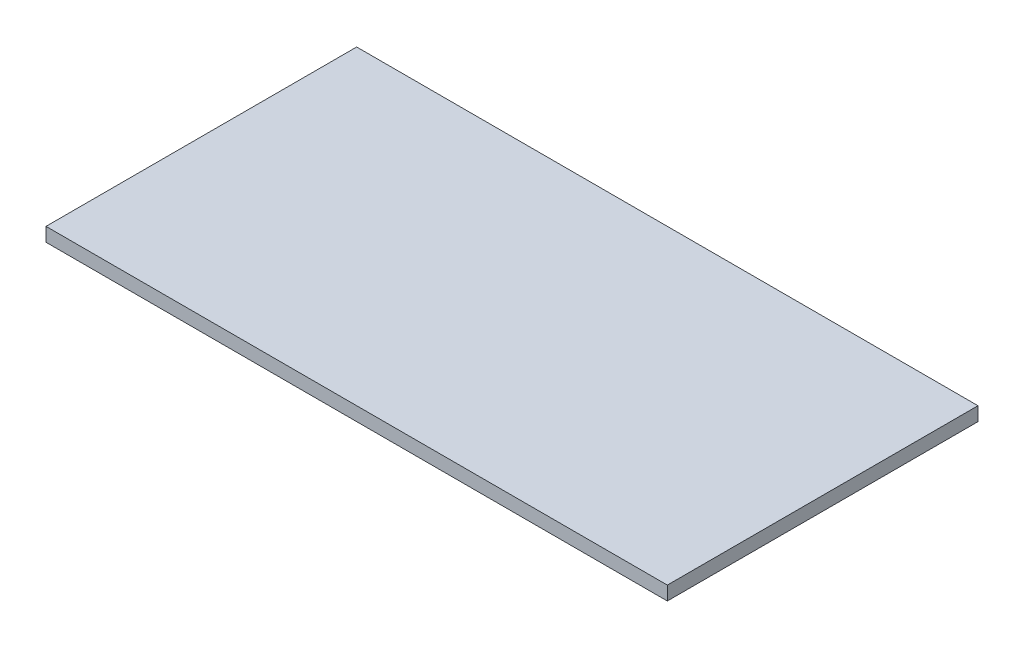
SolidWorks part; units mm, degrees
material "Cedar"
ref_plane "Front Plane" through (0, 0, 0) normal (0, 0, 1) x (1, 0, 0)
ref_plane "Top Plane" through (0, 0, 0) normal (0, 1, 0) x (1, 0, 0)
ref_plane "Right Plane" through (0, 0, 0) normal (1, 0, 0) x (0, 0, -1)
sketch "Sketch1" plane through (0, 0, 0) normal (0, 0, 1) x (1, 0, 0)
  line L1 (-285.75, -6.35) -> (285.75, -6.35)
  line L2 (-285.75, -6.35) -> (-285.75, 6.35)
  line L3 (-285.75, 6.35) -> (285.75, 6.35)
  line L4 (285.75, -6.35) -> (285.75, 6.35)
  line L5 (-285.75, -6.35) -> (285.75, 6.35) construction
  line L6 (-285.75, 6.35) -> (285.75, -6.35) construction
  point P0 (0, 0)
  dimension "D1" = 12.7
  dimension "D2" = 571.5
extrude "Boss-Extrude1" add sketch "Sketch1" against normal blind 285.75
